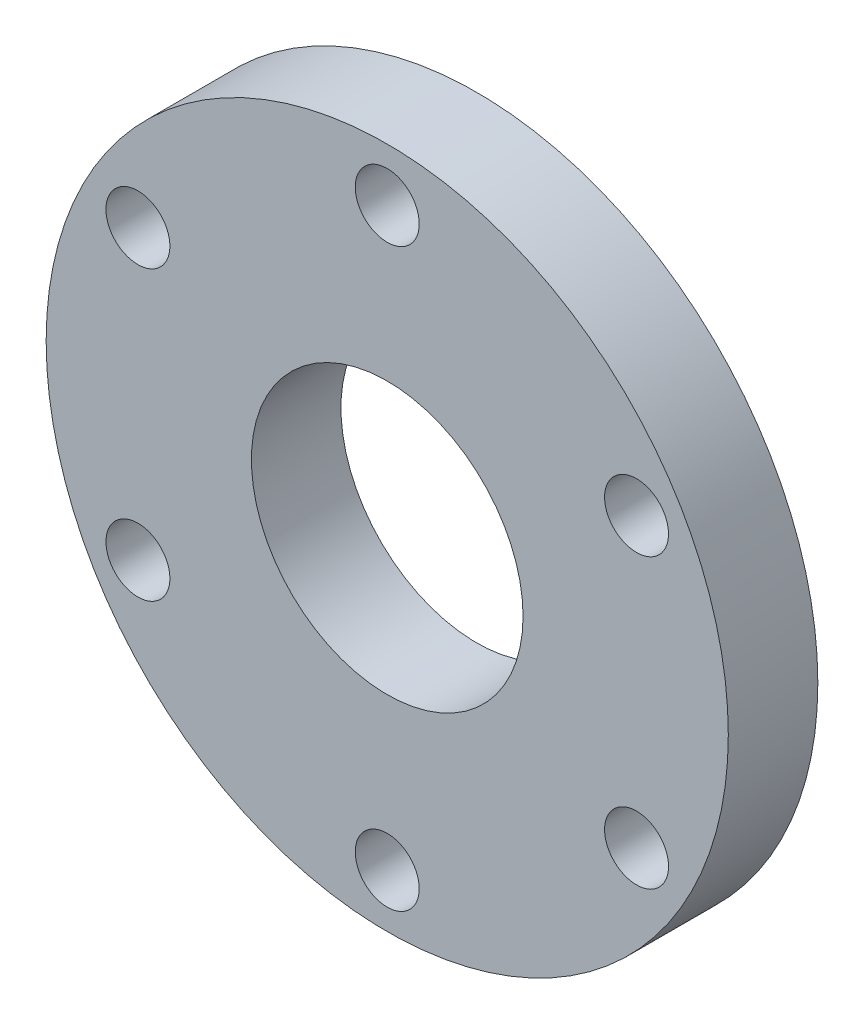
SolidWorks part; units mm, degrees
ref_plane "Front Plane" through (0, 0, 0) normal (0, 0, 1) x (1, 0, 0)
ref_plane "Top Plane" through (0, 0, 0) normal (0, 1, 0) x (1, 0, 0)
ref_plane "Right Plane" through (0, 0, 0) normal (1, 0, 0) x (0, 0, -1)
ref_axis "Axis1" through (0, 0, -88.99) along (0, 0, 1)
sketch "Sketch1" plane through (0, 0, 0) normal (0, 0, 1) x (1, 0, 0)
  circle A0 centre (0, 0) radius 50.8
extrude "Boss-Extrude1" add sketch "Sketch1" along normal mid plane 13.335
sketch "Sketch2" plane through (0, 0, 6.6675) normal (0, 0, 1) x (1, 0, 0)
  circle A0 centre (0, 0) radius 20.2311
extrude "Cut-Extrude1" cut sketch "Sketch2" against normal through all
sketch "Sketch3" plane through (0, 0, 6.6675) normal (0, 0, 1) x (1, 0, 0)
  circle A0 centre (0, 42.8752) radius 4.7625
  dimension "D1" = 9.525
  dimension "D2" = 42.8752
extrude "Cut-Extrude2" cut sketch "Sketch3" against normal through all
pattern_circular "CirPattern1" count 6 over 360 about axis through (0, 0, -88.99) along (0, 0, 1) of "Cut-Extrude2"
